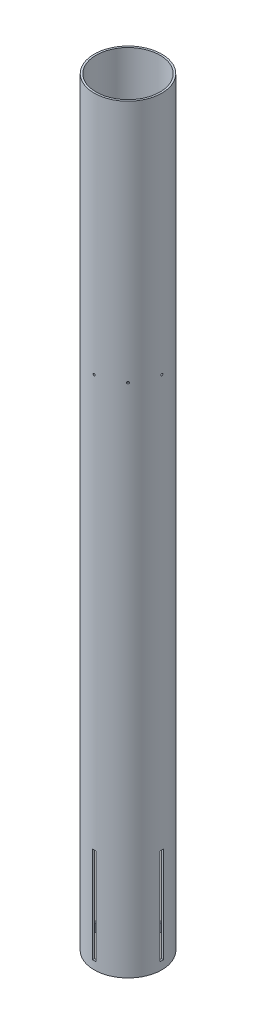
SolidWorks part; units mm, degrees
material "Hexcel AS4C (3000 Filaments)"
ref_plane "Front Plane" through (0, 0, 0) normal (0, 0, 1) x (1, 0, 0)
ref_plane "Top Plane" through (0, 0, 0) normal (0, 1, 0) x (1, 0, 0)
ref_plane "Right Plane" through (0, 0, 0) normal (1, 0, 0) x (0, 0, -1)
sketch "Sketch1" plane through (0, 0, 0) normal (0, 1, 0) x (1, 0, 0)
  circle A0 centre (0, 0) radius 50.8
  dimension "D1" = 101.6
extrude "Body Tube Extrusion" add sketch "Sketch1" along normal blind 1206.5 thin thin type one direction wall 2.921
ref_plane "Plane1" through (0, 0, 53.721) normal (0, 0, 1) x (1, 0, 0)
sketch "Sketch2" plane through (0, 0, 53.721) normal (0, 0, 1) x (1, 0, 0)
  line L0 (0, 1206.5) -> (0, 0) construction
  line L1 (50.8, 1206.5) -> (-50.8, 1206.5) construction
  line L2 (-53.721, 0) -> (53.721, 0) construction
  circle A0 centre (0, 819.15) radius 1.6383
  dimension "D1" = 3.2766
  dimension "D2" = 819.15
extrude "Engine Block Hole" cut sketch "Sketch2" against normal up to next
pattern_circular "CirPattern1" count 8 over 360 about axis through (0, 1206.5, 0) along (0, -1, 0) of "Engine Block Hole"
sketch "Sketch3" plane through (0, 0, 53.721) normal (0, 0, 1) x (1, 0, 0)
  line L0 (0, 0) -> (0, 12.7) construction
  line L1 (-50.8, 0) -> (50.8, 0) construction
  line L2 (0, 1206.5) -> (0, 0) construction
  line L4 (-2.667, 165.1) -> (2.667, 165.1)
  line L5 (-2.667, 165.1) -> (-2.667, 12.7)
  line L6 (-2.667, 12.7) -> (2.667, 12.7)
  line L7 (2.667, 165.1) -> (2.667, 12.7)
  point P10 (0, 12.7)
  dimension "D1" = 152.4
  dimension "D2" = 5.334
  dimension "D3" = 12.7
extrude "Cut-Extrude1" cut sketch "Sketch3" against normal up to next
pattern_circular "CirPattern2" count 4 over 360 about axis through (0, 1206.5, 0) along (0, -1, 0) of "Cut-Extrude1" reverse direction yes
